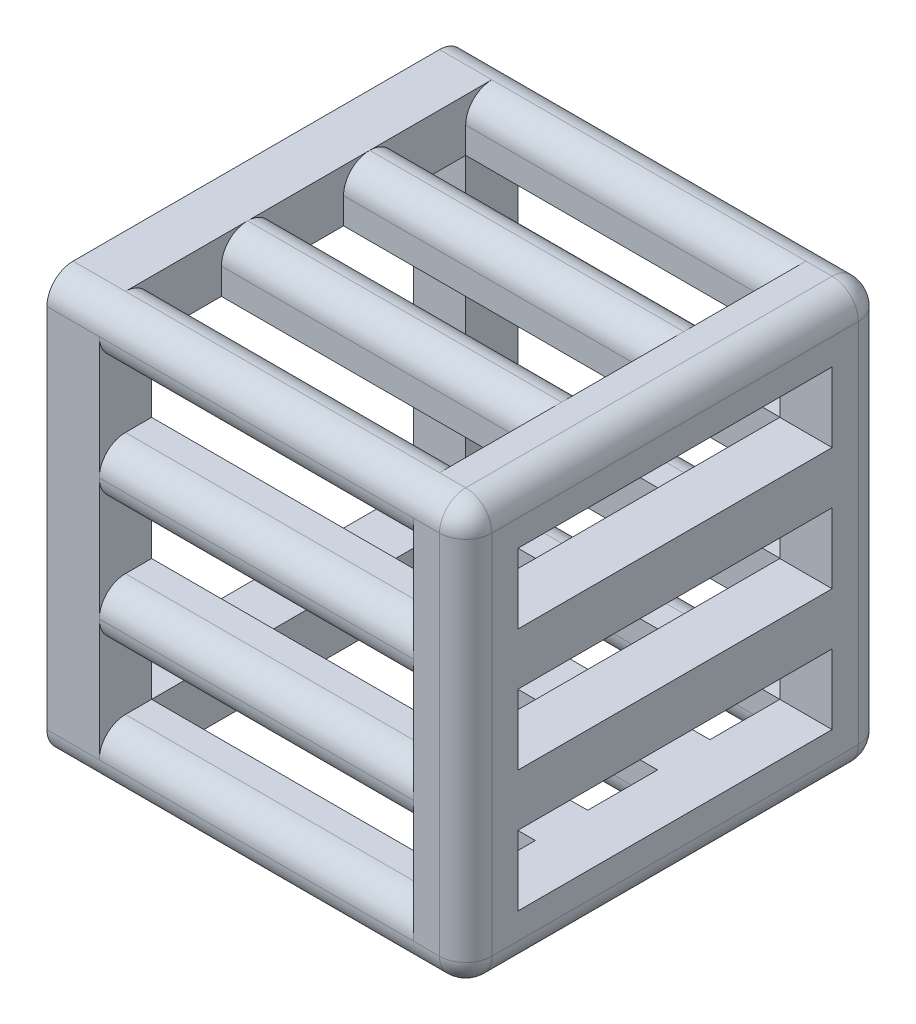
SolidWorks part; units mm, degrees
ref_plane "Front" through (0, 0, 0) normal (0, 0, 1) x (1, 0, 0)
ref_plane "Top" through (0, 0, 0) normal (0, 1, 0) x (1, 0, 0)
ref_plane "Right" through (0, 0, 0) normal (1, 0, 0) x (0, 0, -1)
sketch "草图1" plane through (0, 0, 0) normal (1, 0, 0) x (0, 0, -1)
  line L0 (2, -2) -> (14, -2)
  line L1 (0, 0) -> (16, 0)
  line L2 (0, 0) -> (0, -16)
  line L3 (0, -16) -> (16, -16)
  line L4 (16, 0) -> (16, -16)
  line L5 (14, -2) -> (14, -14)
  line L6 (2, -14) -> (14, -14)
  line L7 (2, -2) -> (2, -14)
  dimension "D1" = 16
  dimension "D2" = 16
  dimension "D3" = 2
extrude "凸台-拉伸1" add sketch "草图1" along normal blind 2
sketch "草图2" plane through (2, 0, 0) normal (1, 0, 0) x (0, 0, -1)
  line L0 (4.6667, 0) -> (4.6667, -2)
  line L1 (0, 0) -> (2, 0)
  line L2 (0, 0) -> (0, -2)
  line L3 (0, -2) -> (2, -2)
  line L4 (2, 0) -> (2, -2)
  line L5 (4.6667, 0) -> (6.6667, 0)
  line L6 (6.6667, 0) -> (6.6667, -2)
  line L7 (4.6667, -2) -> (6.6667, -2)
  line L8 (9.3333, 0) -> (9.3333, -2)
  line L9 (9.3333, 0) -> (11.3333, 0)
  line L10 (11.3333, 0) -> (11.3333, -2)
  line L11 (9.3333, -2) -> (11.3333, -2)
  line L13 (14, -2) -> (16, -2)
  line L14 (14, -2) -> (14, 0)
  line L15 (14, 0) -> (16, 0)
  line L16 (2, -4.67) -> (2, -6.67)
  line L17 (0, -4.67) -> (0, -6.67)
  line L18 (0, -6.67) -> (2, -6.67)
  line L19 (0, -4.67) -> (2, -4.67)
  line L20 (2, -9.34) -> (2, -11.34)
  line L21 (0, -9.34) -> (0, -11.34)
  line L22 (0, -11.34) -> (2, -11.34)
  line L23 (0, -9.34) -> (2, -9.34)
  line L24 (16, -2) -> (16, 0)
  line L25 (2, -14) -> (0, -14)
  line L26 (2, -14) -> (2, -16)
  line L27 (2, -16) -> (0, -16)
  line L28 (11.33, -16) -> (11.33, -14)
  line L29 (16, -16) -> (14, -16)
  line L30 (16, -16) -> (16, -14)
  line L31 (16, -14) -> (14, -14)
  line L32 (14, -16) -> (14, -14)
  line L33 (11.33, -16) -> (9.33, -16)
  line L34 (9.33, -16) -> (9.33, -14)
  line L35 (11.33, -14) -> (9.33, -14)
  line L36 (6.66, -16) -> (6.66, -14)
  line L37 (6.66, -16) -> (4.66, -16)
  line L38 (4.66, -16) -> (4.66, -14)
  line L39 (6.66, -14) -> (4.66, -14)
  line L40 (16, -11.33) -> (16, -9.33)
  line L41 (16, -11.33) -> (14, -11.33)
  line L42 (14, -11.33) -> (14, -9.33)
  line L43 (16, -9.33) -> (14, -9.33)
  line L44 (16, -6.66) -> (16, -4.66)
  line L45 (16, -6.66) -> (14, -6.66)
  line L46 (14, -6.66) -> (14, -4.66)
  line L47 (16, -4.66) -> (14, -4.66)
  line L48 (0, -14) -> (0, -16)
  dimension "D1" = 3
  dimension "D2" = 3
  dimension "D3" = 3
  dimension "D4" = 3
extrude "凸台-拉伸2" add sketch "草图2" along normal blind 12
sketch "草图3" plane through (14, 0, 0) normal (1, 0, 0) x (0, 0, -1)
  line L1 (0, 0) -> (2, 0)
  line L2 (0, 0) -> (0, -16)
  line L3 (0, -16) -> (2, -16)
  line L4 (2, 0) -> (2, -16)
  line L5 (2, -16) -> (16, -16)
  line L6 (2, -16) -> (2, -14)
  line L7 (2, -14) -> (16, -14)
  line L8 (16, -16) -> (16, -14)
  line L9 (16, -14) -> (14, -14)
  line L10 (16, -14) -> (16, 0)
  line L11 (16, 0) -> (14, 0)
  line L12 (14, -14) -> (14, 0)
  line L13 (14, 0) -> (2, 0)
  line L14 (14, 0) -> (14, -2)
  line L15 (14, -2) -> (2, -2)
  line L16 (2, 0) -> (2, -2)
  line L17 (2, -4.67) -> (14, -4.67)
  line L18 (2, -4.67) -> (2, -6.66)
  line L19 (2, -6.66) -> (14, -6.66)
  line L20 (14, -4.67) -> (14, -6.66)
  line L21 (2, -9.34) -> (14, -9.34)
  line L22 (2, -9.34) -> (2, -11.33)
  line L23 (2, -11.33) -> (14, -11.33)
  line L24 (14, -9.34) -> (14, -11.33)
  line M1 (0, 0) -> (0, -2)
  line M2 (0, -2) -> (2, -2)
  line M3 (2, -2) -> (2, 0)
  line M4 (2, 0) -> (0, 0)
extrude "凸台-拉伸3" add sketch "草图3" along normal blind 2 contours M4 M1 M2 M3 | L4 L2 L3 M2 | L5 L8 L7 L4 | L12 L7 L10 L11 | L15 L12 L13 M3 | L4 L19 L12 L17 | L4 L23 L12 L21 region at (14, -1, -1) region at (14, -1, -8) region at (14, -9, -1) region at (14, -7, -15) region at (14, -5.665, -8) region at (14, -15, -9) region at (14, -10.335, -8)
fillet "圆角1" radius 1 8 edges at (8, 0, -16) (8, 0, 0) (8, -16, 0) (16, 0, -8) (16, -8, 0) (16, -16, -8) (16, -8, -16) (8, -16, -16)
fillet "圆角2" radius 1 24 edges at (8, -16, -2) (8, -16, -4.66) (8, -16, -6.66) (8, -16, -9.33) (8, -16, -11.33) (8, -16, -14) (8, -11.33, -16) (8, -6.66, -16) (8, -2, -16) (8, -4.66, -16) (8, -9.33, -16) (8, -14, -16) (8, -14, 0) (8, -11.34, 0) (8, -9.34, 0) (8, -6.67, 0) (8, -4.67, 0) (8, -2, 0) (8, 0, -2) (8, 0, -4.6667) (8, 0, -6.6667) (8, 0, -9.3333) (8, 0, -11.3333) (8, 0, -14)
